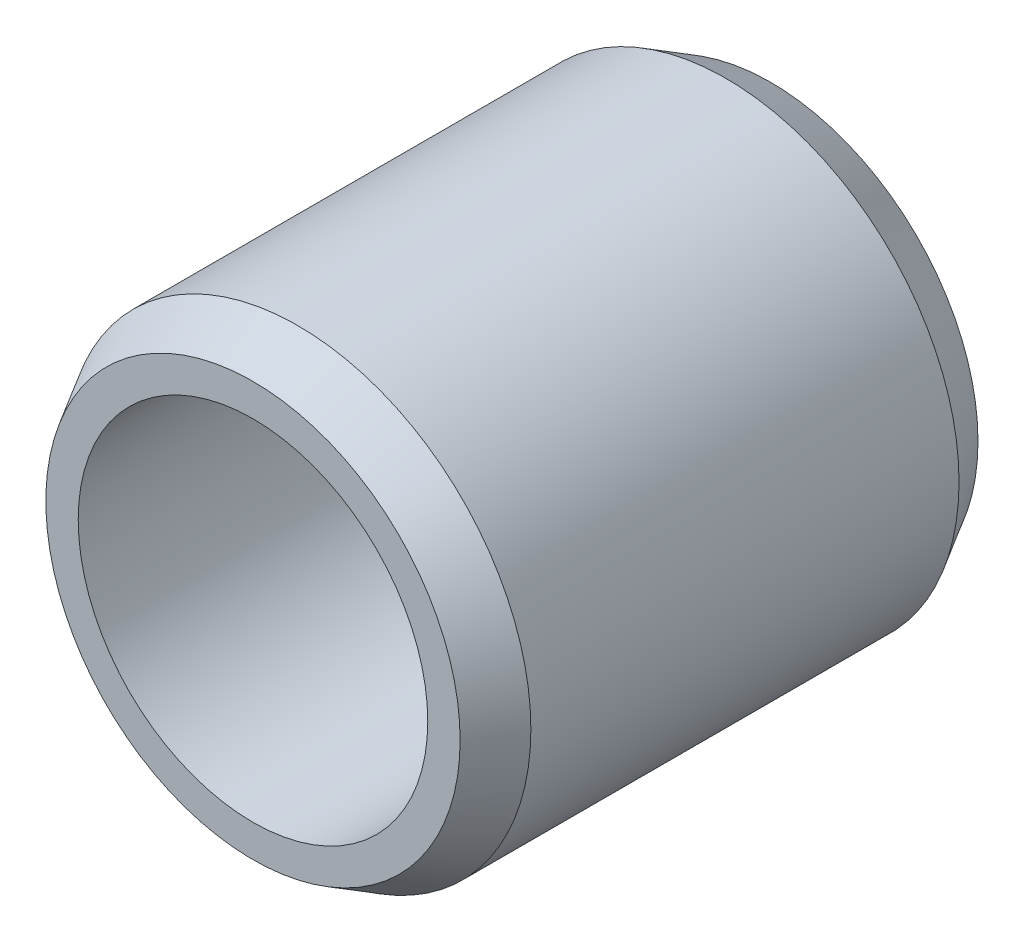
SolidWorks part; units mm, degrees
material "ABS"
ref_plane "Front Plane" through (0, 0, 0) normal (0, 0, 1) x (1, 0, 0)
ref_plane "Top Plane" through (0, 0, 0) normal (0, 1, 0) x (1, 0, 0)
ref_plane "Right Plane" through (0, 0, 0) normal (1, 0, 0) x (0, 0, -1)
sketch "Sketch1" plane through (0, 0, 0) normal (0, 0, 1) x (1, 0, 0)
  circle A0 centre (0, 0) radius 4.5
  circle A1 centre (0, 0) radius 3.375
  dimension "D1" = 6.75
  dimension "D2" = 9
extrude "Boss-Extrude1" add sketch "Sketch1" along normal blind 10
chamfer "Chamfer1" distance 0.5 angle 60 2 edges at (4.5, 0, 10) (4.5, 0, 0) first distance on face at (4.5, 0, 10) first distance on face at (4.5, 0, 0)
